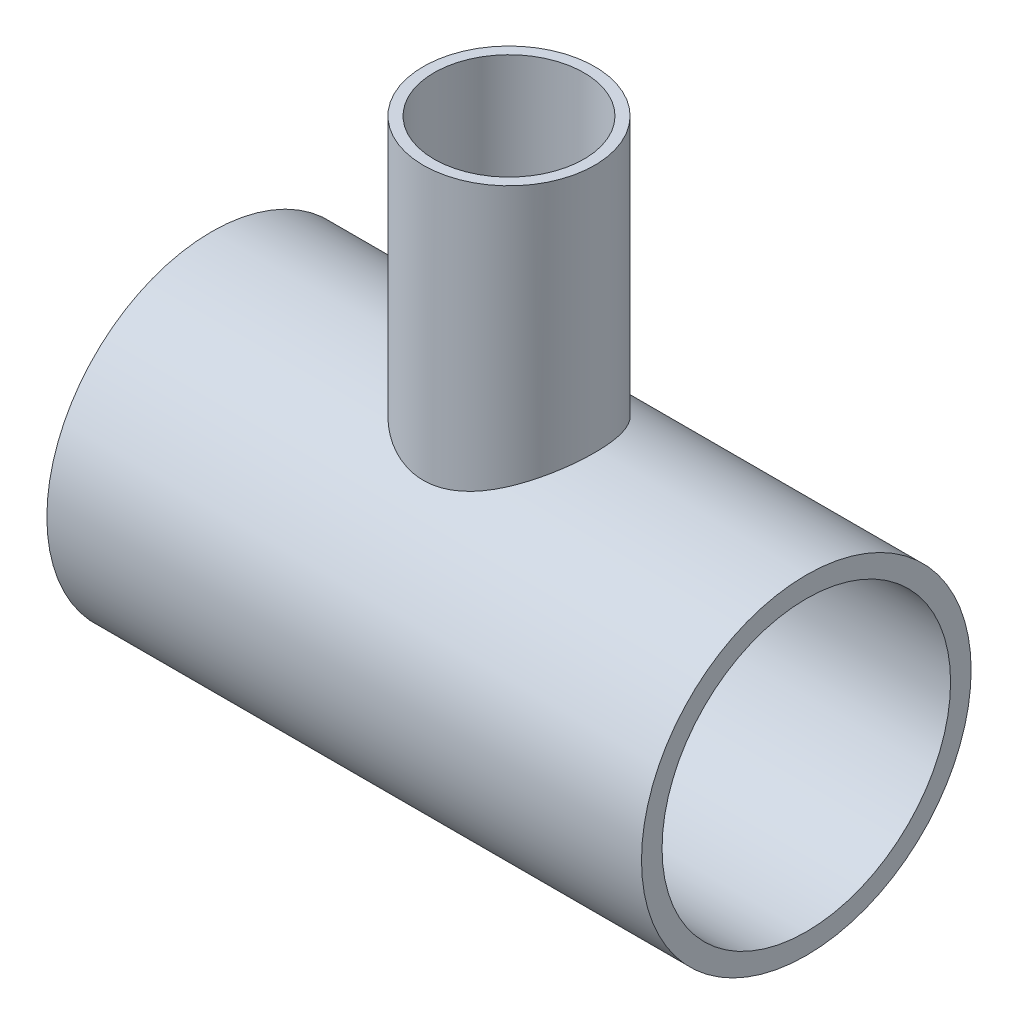
SolidWorks part; units mm, degrees
material "PE High Density"
ref_plane "Front Plane" through (0, 0, 0) normal (0, 0, 1) x (1, 0, 0)
ref_plane "Top Plane" through (0, 0, 0) normal (0, 1, 0) x (1, 0, 0)
ref_plane "Right Plane" through (0, 0, 0) normal (1, 0, 0) x (0, 0, -1)
sketch "Revolve of 12 NOM" plane through (0, 0, 0) normal (0, 0, 1) x (1, 0, 0)
  line L0 (0, 0) -> (319.0916, 0) construction
  line L1 (-292.1, 161.925) -> (292.1, 161.925)
  line L2 (-292.1, 161.925) -> (-292.1, 141.732)
  line L3 (-292.1, 141.732) -> (292.1, 141.732)
  line L4 (292.1, 161.925) -> (292.1, 141.732)
  point P7 (0, 141.732)
  dimension "D1" = 141.732
  dimension "D2" = 161.925
  dimension "D3" = 584.2
revolve "Revolve12 NOM" add sketch "Revolve of 12 NOM" angle 360 about L0
ref_plane "Offset B Plane" through (0, 406.4, 0) normal (0, 1, 0) x (1, 0, 0)
sketch "Sketch2" plane through (0, 406.4, 0) normal (0, 1, 0) x (1, 0, 0)
  line L0 (-55, 0) -> (55, 0) construction
  line L1 (292.1, -161.925) -> (292.1, 161.925) construction
  circle A0 centre (0, 0) radius 84.1375
  dimension "D2" = 168.275
  dimension "D1" = 292.1
extrude "6 NOM OD Extrude" add sketch "Sketch2" against normal up to surface (268.0505 mm away) up to face at (-292.1, 0, 161.925)
sketch "6 NOM ID Extrude" plane through (0, 406.4, 0) normal (0, 1, 0) x (1, 0, 0)
  circle A0 centre (0, 0) radius 73.6473
  dimension "D1" = 147.2946
extrude "6 NOM ID Extrude Cut" cut sketch "6 NOM ID Extrude" against normal up to surface (406.4 mm away) up to plane "Top Plane"
ref_axis "Nozzle" through (0, 115.9252, 0) along (0, 1, 0)
ref_plane "Midplane" through (0, 0, 0) normal (1, 0, 0) x (0, 0, -1)
sketch "Sketch3" plane through (0, 406.4, 0) normal (0, 1, 0) x (1, 0, 0)
  point P0 (0, 0)
equation "\"A\"= 8in'EPG Datasheet"
equation "\"B\"= 16in'EPG Datasheet"
equation "\"L\"= 23in'EPG Datasheet"
equation "\"ID 12\"= 11.16in'EPG Datasheet"
equation "\"OD 12\"= 12.75in'EPG Datasheet"
equation "\"ID 6\"= 5.799in'EPG Datasheet"
equation "\"OD 6\"= 6.625in'EPG Datasheet"
equation "\"D1@Revolve of 12 NOM\" = \"ID 12\" / 2"
equation "\"D2@Revolve of 12 NOM\" = \"OD 12\" / 2"
equation "\"D3@Revolve of 12 NOM\" = \"L\""
equation "\"D1@Sketch2\"=\"L\"/2"
equation "\"D2@Sketch2\"=\"OD 6\""
equation "\"D1@6 NOM ID Extrude\" = \"ID 6\""
